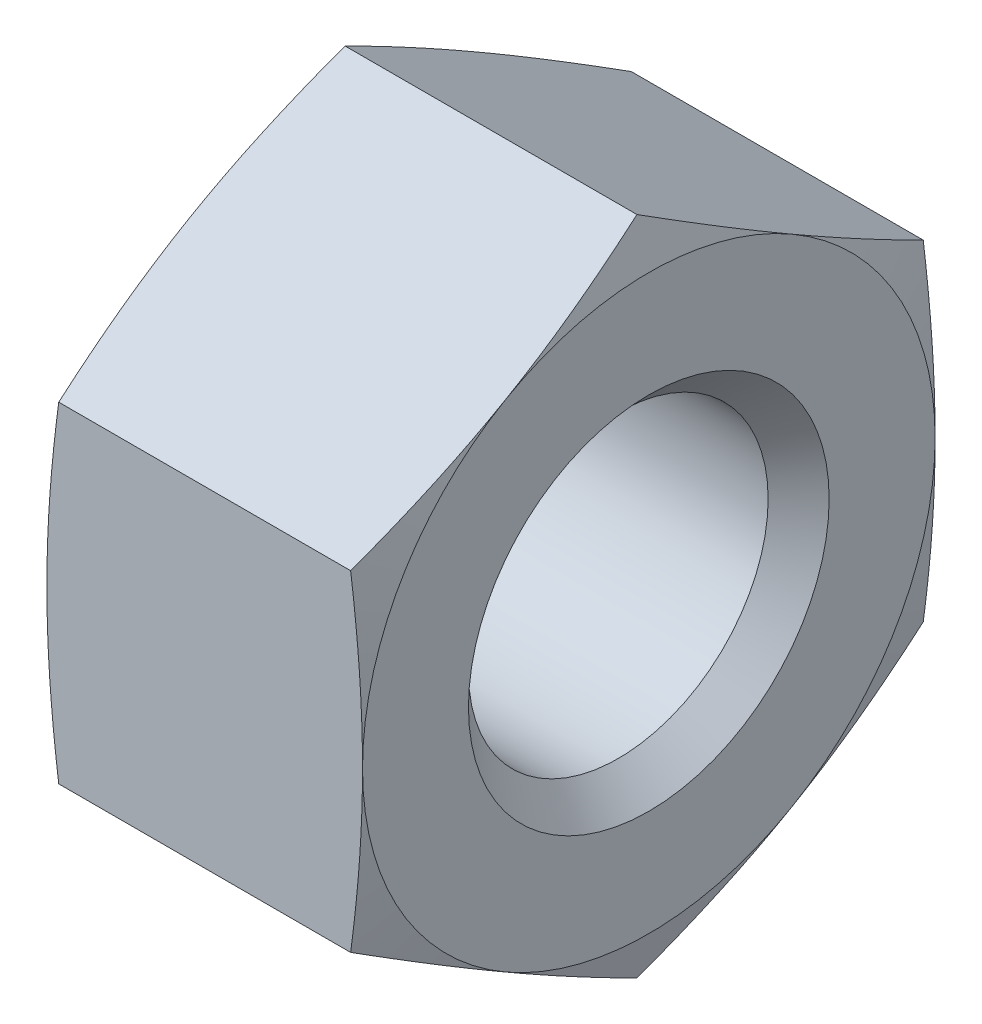
SolidWorks part; units mm, degrees
ref_plane "前视基准面" through (0, 0, 0) normal (0, 0, 1) x (1, 0, 0)
ref_plane "上视基准面" through (0, 0, 0) normal (0, 1, 0) x (1, 0, 0)
ref_plane "右视基准面" through (0, 0, 0) normal (1, 0, 0) x (0, 0, -1)
sketch "草图1" plane through (0, 0, 0) normal (0, 0, 1) x (1, 0, 0)
  line L0 (-3.5, 0) -> (-3.5, 6.35)
  line L1 (-3.5, 6.35) -> (-2.8446, 8.796)
  line L2 (-2.8446, 8.796) -> (2.8446, 8.796)
  line L3 (2.8446, 8.796) -> (3.5, 6.35)
  line L4 (3.5, 6.35) -> (3.5, 0)
  line L5 (3.5, 0) -> (-3.5, 0)
  line L6 (3.5, 0) -> (-3.5, 0) construction
revolve "旋转1" add sketch "草图1" angle 360 about L6 reverse direction yes
sketch "草图2" plane through (0, 0, 0) normal (0, 0, 1) x (1, 0, 0)
  line L0 (-3.5, 0) -> (-3.5, 4)
  line L1 (-3.5, 4) -> (-2.8235, 3.3235)
  line L2 (-2.8235, 3.3235) -> (2.8235, 3.3235)
  line L3 (2.8235, 3.3235) -> (3.5, 4)
  line L4 (3.5, 4) -> (3.5, 0)
  line L5 (3.5, 0) -> (-3.5, 0)
  line L6 (3.5, 0) -> (-3.5, 0) construction
revolve "切除-旋转1" cut sketch "草图2" angle 360 about L6 reverse direction yes
cosmetic thread "装饰螺纹线1" parameters "D1"=7, "D2"=8
sketch "草图3" plane through (0, 0, 0) normal (1, 0, 0) x (0, 0, -1)
  line L0 (-12.7, 12.7) -> (-12.7, -12.7)
  line L1 (-12.7, -12.7) -> (12.7, -12.7)
  line L2 (12.7, -12.7) -> (12.7, 12.7)
  line L3 (12.7, 12.7) -> (-12.7, 12.7)
  line L4 (-6.35, 3.6662) -> (-6.35, -3.6662)
  line L5 (-6.35, -3.6662) -> (0, -7.3323)
  line L6 (0, -7.3323) -> (6.35, -3.6662)
  line L7 (6.35, -3.6662) -> (6.35, 3.6662)
  line L8 (6.35, 3.6662) -> (0, 7.3323)
  line L9 (0, 7.3323) -> (-6.35, 3.6662)
extrude "切除-拉伸1" cut sketch "草图3" along normal blind 3.5 and the other way blind 3.5
ref_plane "基准面1" through (-3.5, 0, 0) normal (1, 0, 0) x (0, 0, -1)
ref_plane "nut XY" through (0, 0, 0) normal (1, 0, 0) x (0, 0, -1)
ref_plane "nut XZ" through (0, 0, 0) normal (0, -1, 0) x (-1, 0, 0)
ref_plane "nut YZ" through (0, 0, 0) normal (0, 0, -1) x (-1, 0, 0)
ref_axis "nut X" through (0, 0, 80.9) along (0, 0, -1)
ref_axis "nut Y" through (0, -50, 0) along (0, 1, 0)
ref_axis "nut Z" through (80.9, 0, 0) along (-1, 0, 0)
sketch3d "nut"
  point P0 (0, 0, 0)
ref_plane "nut1 XY" through (-3.5, 0, 0) normal (1, 0, 0) x (0, 0, -1)
ref_plane "nut1 XZ" through (0, 0, 0) normal (0, -1, 0) x (-1, 0, 0)
ref_plane "nut1 YZ" through (0, 0, 0) normal (0, 0, -1) x (-1, 0, 0)
ref_axis "nut1 X" through (-3.5, 0, 80.9) along (0, 0, -1)
ref_axis "nut1 Y" through (-3.5, -50, 0) along (0, 1, 0)
ref_axis "nut1 Z" through (80.9, 0, 0) along (-1, 0, 0)
sketch3d "nut1"
  point P0 (-3.5, 0, 0)
ref_plane "nut_to_body XY" through (0, 0, 0) normal (0, 0, 1) x (1, 0, 0)
ref_plane "nut_to_body XZ" through (0, 0, 0) normal (0, -1, 0) x (-1, 0, 0)
ref_plane "nut_to_body YZ" through (-3.5, 0, 0) normal (1, 0, 0) x (0, 0, -1)
ref_axis "nut_to_body X" through (-80.9, 0, 0) along (1, 0, 0)
ref_axis "nut_to_body Y" through (-3.5, -50, 0) along (0, 1, 0)
ref_axis "nut_to_body Z" through (-3.5, 0, 80.9) along (0, 0, -1)
sketch3d "nut_to_body"
  point P0 (-3.5, 0, 0)
equation "\"零件重量\"= \"SW-质量\""
